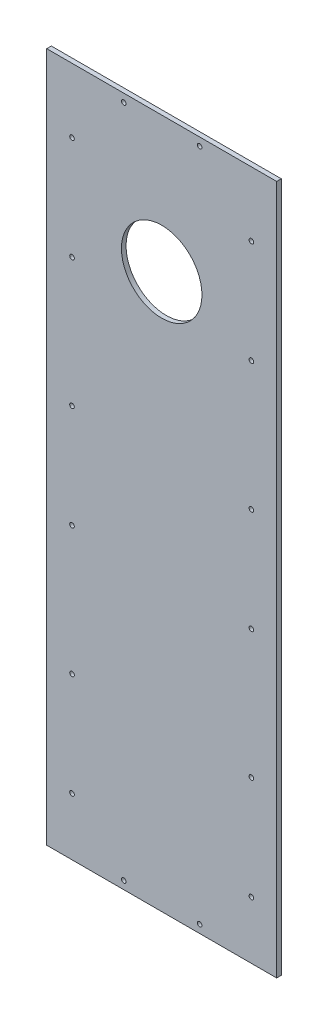
SolidWorks part; units mm, degrees
material "Alumina"
ref_plane "Front Plane" through (0, 0, 0) normal (0, 0, 1) x (1, 0, 0)
ref_plane "Top Plane" through (0, 0, 0) normal (0, 1, 0) x (1, 0, 0)
ref_plane "Right Plane" through (0, 0, 0) normal (1, 0, 0) x (0, 0, -1)
sketch "Sketch1" plane through (0, 0, 0) normal (0, 0, 1) x (1, 0, 0)
  line L1 (50, -150) -> (-50, -150)
  line L2 (50, -150) -> (50, 150)
  line L3 (50, 150) -> (-50, 150)
  line L4 (-50, -150) -> (-50, 150)
  line L5 (50, -150) -> (-50, 150) construction
  line L6 (50, 150) -> (-50, -150) construction
  point P0 (0, 0)
  dimension "D1" = 100
  dimension "D2" = 300
extrude "Boss-Extrude1" add sketch "Sketch1" along normal blind 2
sketch "Sketch2" plane through (0, 0, 2) normal (0, 0, 1) x (1, 0, 0)
  line L0 (-50, 150) -> (-50, -150) construction
  line L1 (50, 150) -> (-50, 150) construction
  line L2 (-50, -150) -> (50, -150) construction
  line L4 (0, -1.1) -> (0, 1.1) construction
  line L5 (-39, 122) -> (-39, 21) construction
  circle A0 centre (-39, 122) radius 1
  circle A1 centre (-39, 77) radius 1
  circle A2 centre (39, 122) radius 1
  circle A3 centre (39, 77) radius 1
  circle A4 centre (-39, 21) radius 1
  circle A5 centre (-39, -24) radius 1
  circle A6 centre (39, 21) radius 1
  circle A7 centre (39, -24) radius 1
  circle A8 centre (-39, -80) radius 1
  circle A9 centre (-39, -125) radius 1
  circle A10 centre (39, -80) radius 1
  circle A11 centre (39, -125) radius 1
  circle A13 centre (16.5, -146.5) radius 1
  circle A14 centre (-16.5, -146.5) radius 1
  circle A15 centre (-16.5, 146.5) radius 1
  circle A16 centre (16.5, 146.5) radius 1
  dimension "D1" = 2
  dimension "D3" = 28
  dimension "D4" = 2
  dimension "D6" = 11
  dimension "D10" = 2
  dimension "D11" = 33
  dimension "D13" = 3.5
  dimension "D14" = 78
  dimension "D15" = 11
  dimension "D5" = 3.5
  dimension "D2" = 11
  dimension "D9" = 25
  dimension "D17" = 101
  dimension "D7" = 2
  dimension "D8" = 3
  dimension "D12" = 2
extrude "Cut-Extrude1" cut sketch "Sketch2" against normal blind 10
sketch "Sketch3" plane through (0, 0, 0) normal (0, 0, -1) x (-1, 0, 0)
  line L0 (-50, 150) -> (50, 150) construction
  line L1 (-50, -150) -> (-50, 150) construction
  circle A0 centre (0, 91) radius 17.5
  dimension "D2" = 35
  dimension "D3" = 50
  dimension "D1" = 59
extrude "Cut-Extrude2" cut sketch "Sketch3" against normal blind 10
